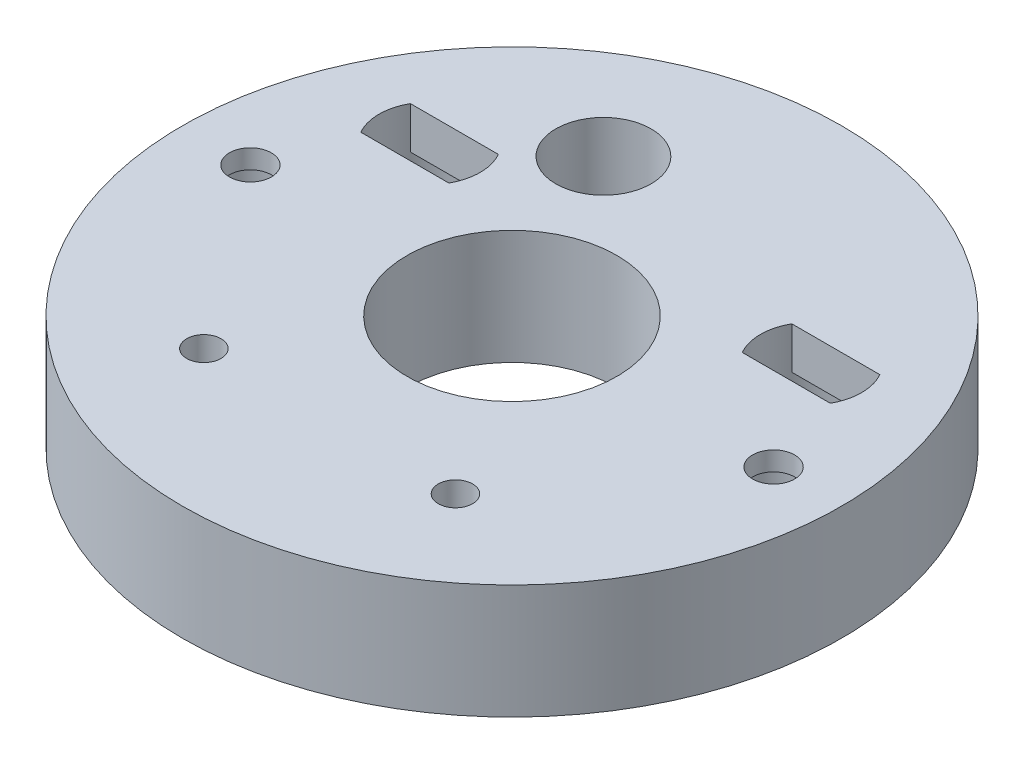
SolidWorks part; units mm, degrees
ref_plane "前视基准面" through (0, 0, 0) normal (0, 0, 1) x (1, 0, 0)
ref_plane "上视基准面" through (0, 0, 0) normal (0, 1, 0) x (1, 0, 0)
ref_plane "右视基准面" through (0, 0, 0) normal (1, 0, 0) x (0, 0, -1)
sketch "草图1" plane through (0, 0, 0) normal (0, 1, 0) x (1, 0, 0)
  line L0 (10, 5.6789) -> (-10, 5.6789) construction
  line L1 (0, 0) -> (0, 21.4139) construction
  line L2 (-6.595, -9.5611) -> (6.595, -9.5611) construction
  line L3 (-0.6445, -0.366) -> (22.2352, 12.6272) construction
  line L4 (0, 0) -> (2.6547, 0) construction
  circle A0 centre (0, 0) radius 17.28
  circle A1 centre (0, 0) radius 5 construction
  circle A2 centre (0, 0) radius 5.5
  circle A3 centre (10, 5.6789) radius 2.5 construction
  circle A4 centre (-10, 5.6789) radius 2.5 construction
  circle A5 centre (6.595, -9.5611) radius 1.76 construction
  circle A6 centre (-6.595, -9.5611) radius 1.76 construction
  circle A7 centre (-10, 5.6789) radius 2.65
  circle A8 centre (-6.595, -9.5611) radius 1.9
  circle A9 centre (6.595, -9.5611) radius 1.9
  circle A10 centre (10, 5.6789) radius 2.65
  point P14 (0, 5.6789)
  point P21 (0, -9.5611)
  dimension "D1" = 34.56
  dimension "D2" = 10
  dimension "D3" = 11
  dimension "D5" = 11.5
  dimension "D7" = 5
  dimension "D8" = 13.19
  dimension "D4" = 20
  dimension "D6" = 3.52
  dimension "D10" = 5.3
  dimension "D11" = 3.8
  dimension "D12" = 10
  dimension "D9" = 15.24
  dimension "D13" = 5.6789
  dimension "D14" = 9.5611
  dimension "D15" = 6.595
extrude "凸台-拉伸1" add sketch "草图1" along normal blind 3.8
sketch "草图2" plane through (0, 3.8, 0) normal (0, 1, 0) x (1, 0, 0)
  line L0 (-7.35, 18.1851) -> (-7.35, -3.106) construction
  line L1 (0, -200000) -> (0, 200021.4139) construction
  line L2 (0, 0) -> (-3.9187, 0) construction
  circle A1 centre (0, 0) radius 17.28
  circle A2 centre (0, 0) radius 17.28 construction
  circle A3 centre (-10, 5.6789) radius 2.5 construction
  circle A4 centre (-4.85, 9.6447) radius 2.5
  circle A6 centre (-10, 5.6789) radius 2.65 construction
  dimension "D2" = 6.5
  dimension "D3" = 5
  dimension "D4" = 4.85
  dimension "D5" = 9.6447
  dimension "D1" = 0
extrude "切除-拉伸1" cut sketch "草图2" against normal through all
sketch "草图3" plane through (0, 3.8, 0) normal (0, 1, 0) x (1, 0, 0)
  line L0 (-12.3092, 4.3789) -> (-7.6908, 4.3789)
  line L1 (-12.3092, 6.9789) -> (-7.6908, 6.9789)
  line L2 (-10, 6.9789) -> (-10, 4.3789) construction
  line L3 (0, 0) -> (0, 3.4524) construction
  line L4 (12.3092, 4.3789) -> (7.6908, 4.3789)
  line L5 (12.3092, 6.9789) -> (7.6908, 6.9789)
  circle A0 centre (6.595, -9.5611) radius 1.9 construction
  circle A1 centre (0, 0) radius 17.28
  circle A2 centre (0, 0) radius 17.28
  circle A3 centre (-6.595, -9.5611) radius 1.9 construction
  circle A5 centre (-10, 5.6789) radius 2.65 construction
  circle A6 centre (0, 0) radius 5.5 construction
  circle A7 centre (-4.85, 9.6447) radius 2.5 construction
  circle A8 centre (6.595, -9.5611) radius 1.9 construction
  circle A9 centre (-6.595, -9.5611) radius 1.9 construction
  arc A11 (-12.3092, 6.9789) -> (-12.3092, 4.3789) centre (-10, 5.6789) ccw
  circle A12 centre (0, 0) radius 5.5
  circle A13 centre (-4.85, 9.6447) radius 2.5
  arc A14 (-7.6908, 4.3789) -> (-7.6908, 6.9789) centre (-10, 5.6789) ccw
  arc A15 (7.6908, 4.3789) -> (7.6908, 6.9789) centre (10, 5.6789) cw
  arc A16 (12.3092, 6.9789) -> (12.3092, 4.3789) centre (10, 5.6789) cw
  circle A17 centre (-6.595, -9.5611) radius 0.9
  circle A18 centre (6.595, -9.5611) radius 0.9
  dimension "D3" = 1.8
  dimension "D2" = 2.6
  dimension "D1" = 0
extrude "凸台-拉伸2" add sketch "草图3" along normal blind 2.2
sketch "草图4" plane through (0, 6, 0) normal (0, 1, 0) x (1, 0, 0)
  line L0 (0, 0) -> (-31.0846, 0) construction
  circle A0 centre (-13.717, 0) radius 1.1
  circle A1 centre (13.717, 0) radius 1.1
  dimension "D1" = 13.717
  dimension "D3" = 2.2
  dimension "D4" = 2.2
  dimension "D2" = 13.717
extrude "切除-拉伸2" cut sketch "草图4" against normal through all
sketch "草图5" plane through (0, 0, 0) normal (0, -1, 0) x (1, 0, 0)
  line L0 (0, 0) -> (27.0843, 0) construction
  circle A0 centre (13.717, 0) radius 1.7
  circle A1 centre (-13.717, 0) radius 1.7
  dimension "D1" = 3.4
  dimension "D2" = 3.4
extrude "切除-拉伸3" cut sketch "草图5" against normal blind 5
